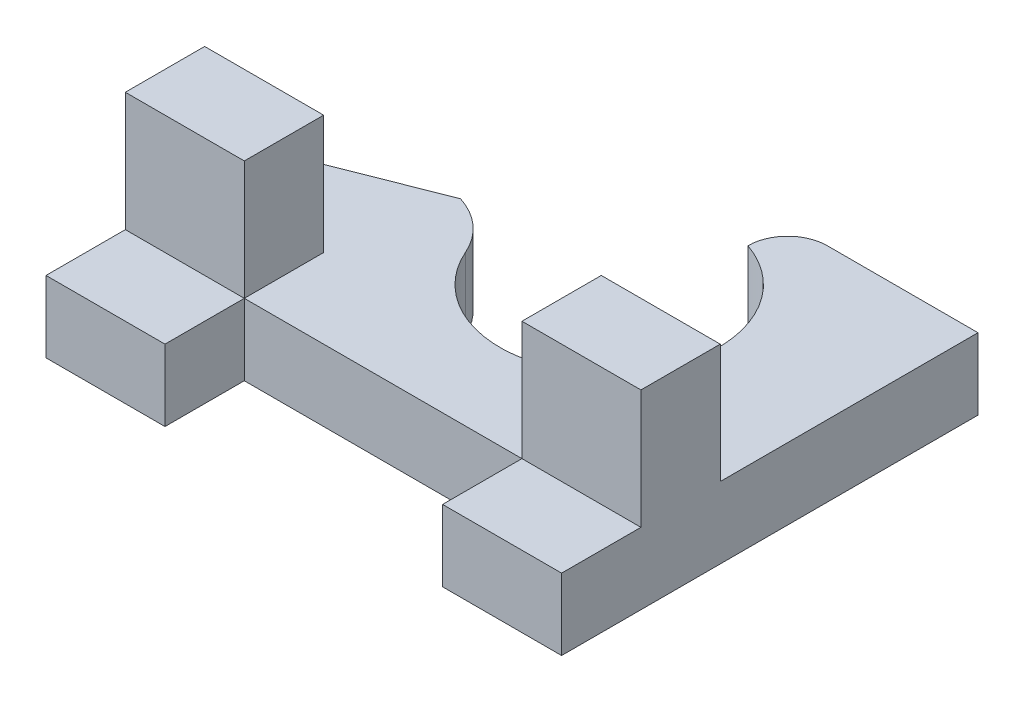
SolidWorks part; units mm, degrees
ref_plane "Front Plane" through (0, 0, 0) normal (0, 0, 1) x (1, 0, 0)
ref_plane "Top Plane" through (0, 0, 0) normal (0, 1, 0) x (1, 0, 0)
ref_plane "Right Plane" through (0, 0, 0) normal (1, 0, 0) x (0, 0, -1)
sketch "Sketch1" plane through (0, 0, 0) normal (0, 1, 0) x (1, 0, 0)
  line L0 (6.5, 2.5) -> (6.5, 0)
  line L1 (3.5, 0) -> (-3.5, 0)
  line L2 (-6.5, 0) -> (-6.5, 2.5)
  line L5 (-6.5, 2.5) -> (-6.5, 3.5)
  line L7 (6.5, 0) -> (6.5, -2)
  line L8 (6.5, -2) -> (3.5, -2)
  line L9 (3.5, 0) -> (3.5, -2)
  line L11 (-6.5, 0) -> (-6.5, -2)
  line L12 (-6.5, -2) -> (-3.5, -2)
  line L13 (-3.5, 0) -> (-3.5, -2)
  line L15 (6.5, 4.9) -> (6.5, 2.5)
  line L17 (-1.95, 4.9) -> (-2.95, 4.9)
  line L18 (-2.95, 4.9) -> (-6.5, 3.5)
  line L19 (1.7, 7.4986) -> (1.7, 8.4986)
  line L20 (1.7, 8.4986) -> (6.5, 8.4986)
  line L21 (6.5, 8.4986) -> (6.5, 4.9)
  arc A2 (-1.95, 4.9) -> (3.3581, 3.8908) centre (0.8, 4.9) ccw
  arc A3 (3.3581, 3.8908) -> (1.7, 7.4986) centre (0.8, 4.9) ccw
  point P0 (0, 0)
  dimension "D1" = 2.4
  dimension "D2" = 5.5
  dimension "D3" = 13
  dimension "D4" = 7.3
  dimension "D5" = 2.5
  dimension "D6" = 1
  dimension "D7" = 1
  dimension "D8" = 2
  dimension "D9" = 3
  dimension "D10" = 3.3
  dimension "D11" = 2.4
  dimension "D12" = 1
  dimension "D13" = 4.8
extrude "Boss-Extrude1" add sketch "Sketch1" along normal blind 1.8
fillet "Fillet1" radius 2 1 edges at (-1.95, 0.9, -4.9)
fillet "Fillet3" radius 1 1 edges at (1.7, 0.9, -8.4986)
ref_plane "Plane1" through (0, 1.8, 0) normal (0, 1, 0) x (1, 0, 0)
sketch "Sketch2" plane through (0, 1.8, 0) normal (0, 1, 0) x (1, 0, 0)
  line L0 (-6.5, 3.5) -> (-6.5, -2) construction
  line L1 (-3.5, 0) -> (-6.5, 0)
  line L2 (-3.5, 0) -> (-3.5, 2)
  line L3 (-3.5, 2) -> (-6.5, 2)
  line L4 (-6.5, 0) -> (-6.5, 2)
  line L5 (6.5, -2) -> (6.5, 8.4986) construction
  line L6 (3.5, 0) -> (6.5, 0)
  line L7 (3.5, 0) -> (3.5, 2)
  line L8 (3.5, 2) -> (6.5, 2)
  line L9 (6.5, 0) -> (6.5, 2)
  dimension "D1" = 2
extrude "Boss-Extrude2" add sketch "Sketch2" along normal blind 3
